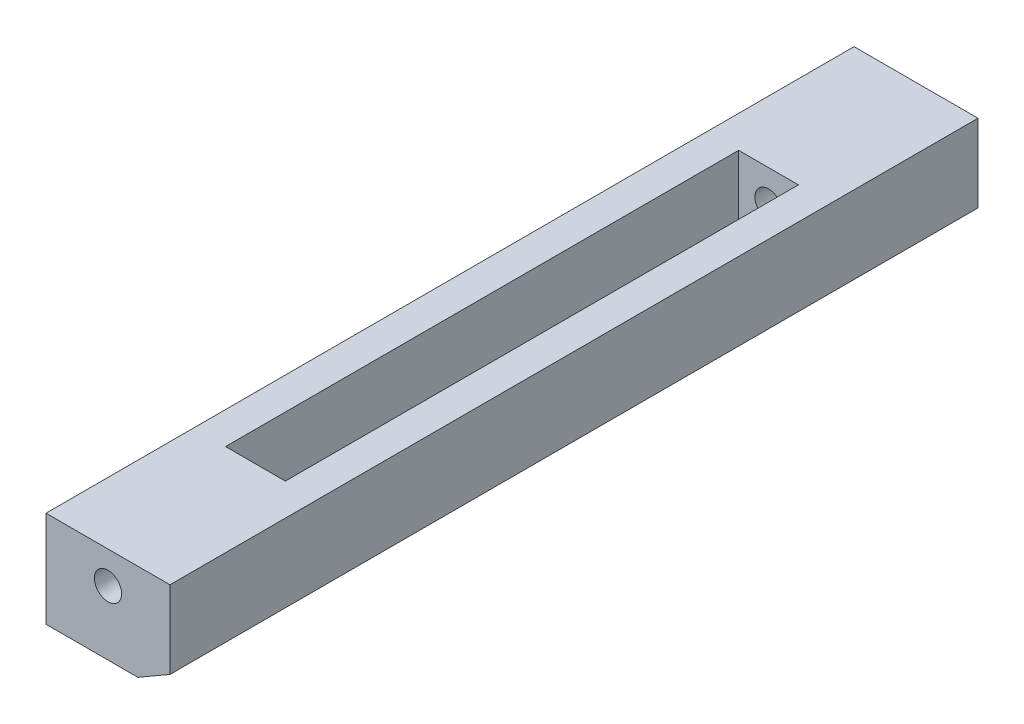
SolidWorks part; units mm, degrees
ref_plane "Front Plane" through (0, 0, 0) normal (0, 0, 1) x (1, 0, 0)
ref_plane "Top Plane" through (0, 0, 0) normal (0, 1, 0) x (1, 0, 0)
ref_plane "Right Plane" through (0, 0, 0) normal (1, 0, 0) x (0, 0, -1)
sketch "Sketch1" plane through (0, 0, 0) normal (0, 1, 0) x (1, 0, 0)
  line L1 (-6.1357, -40) -> (6.1357, -40)
  line L2 (-6.1357, -40) -> (-6.1357, 40)
  line L3 (-6.1357, 40) -> (6.1357, 40)
  line L4 (6.1357, -40) -> (6.1357, 40)
  line L5 (-6.1357, -40) -> (6.1357, 40) construction
  line L6 (-6.1357, 40) -> (6.1357, -40) construction
  line L11 (-2.9607, -25.4) -> (2.9607, -25.4)
  line L12 (-2.9607, -25.4) -> (-2.9607, 25.4)
  line L13 (-2.9607, 25.4) -> (2.9607, 25.4)
  line L14 (2.9607, -25.4) -> (2.9607, 25.4)
  line L15 (-2.9607, -25.4) -> (2.9607, 25.4) construction
  line L16 (-2.9607, 25.4) -> (2.9607, -25.4) construction
  point P0 (0, 0)
  point P6 (0, 0)
  dimension "D1" = 12.2715
  dimension "D2" = 80
  dimension "D3" = 3.175
  dimension "D4" = 50.8
extrude "Boss-Extrude1" add sketch "Sketch1" along normal blind 3.175 and the other way blind 6.35
sketch "Sketch4" plane through (0, 0, 40) normal (0, 0, 1) x (1, 0, 0)
  circle A0 centre (0, 0) radius 1.35
  dimension "D1" = 2.7
extrude "Cut-Extrude1" cut sketch "Sketch4" against normal through all
chamfer "Chamfer1" distance 3.175 angle 30 1 edges at (6.1357, -6.35, 0) first distance on face at (0, -6.35, 0)
equation "\"tighttol\" = 0.005in"
equation "\"normtol\" = 0.01in"
equation "\"loosetol\" = 0.02in"
equation "\"Fry height\"= 0.5in"
equation "\"Fry spacing\"= 0.5625in"
equation "\"Potato width\"= \"Fry spacing\" * 4"
equation "\"Potato length\"= 80mm"
equation "\"D1@Sketch1\"=\"Fry spacing\" - 2 * \"loosetol\"-1mm"
equation "\"D2@Sketch1\"=\"Potato length\""
equation "\"D1@Sketch4\"=2.7mm"
